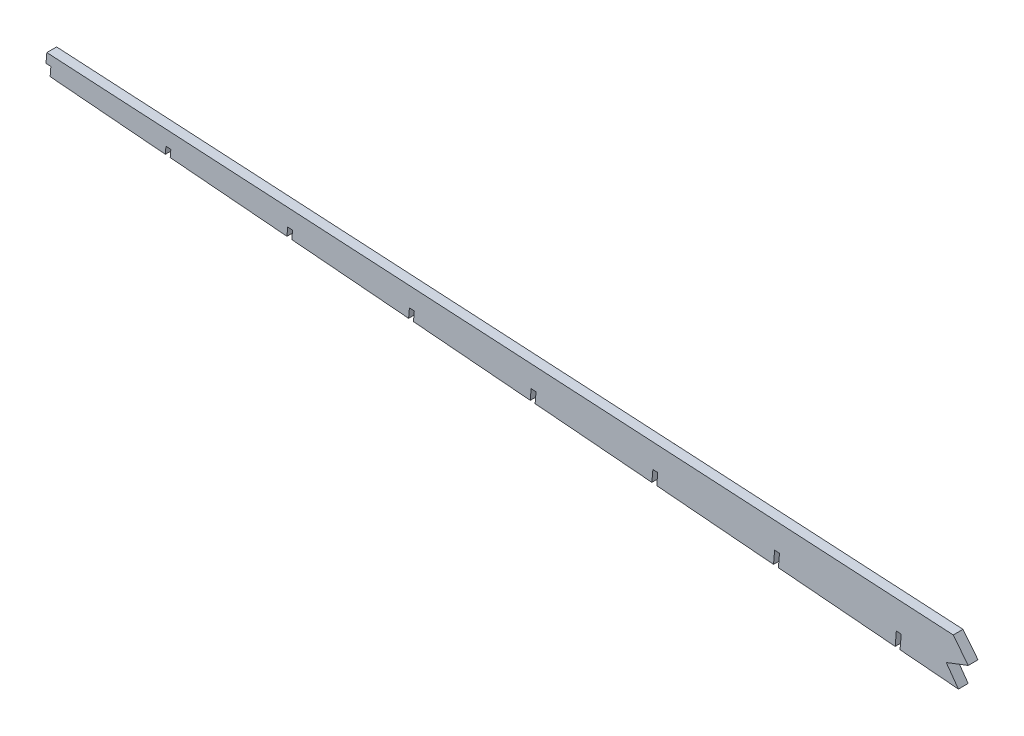
SolidWorks part; units mm, degrees
material "Balsa"
ref_plane "Front Plane" through (0, 0, 0) normal (0, 0, 1) x (1, 0, 0)
ref_plane "Top Plane" through (0, 0, 0) normal (0, 1, 0) x (1, 0, 0)
ref_plane "Right Plane" through (0, 0, 0) normal (1, 0, 0) x (0, 0, -1)
sketch "Sketch1" plane through (0, 0, 0) normal (0, 0, 1) x (1, 0, 0)
  line L0 (76.2, 56.7475) -> (76.2, 37.6975)
  line L1 (79.375, 56.7475) -> (79.375, 37.6975)
  line L2 (0, 44.0475) -> (0, 31.3475)
  line L3 (3.175, 44.0475) -> (3.175, 31.3475)
  line L4 (-5.7133, 44.4467) -> (-6.776, 31.7912)
  line L5 (-2.5494, 44.181) -> (-3.6121, 31.5255)
  line L6 (-1.4923, 31.3475) -> (25.4, 31.3475)
  line L7 (25.4, 31.3475) -> (69.85, 37.6975)
  line L8 (-2.5494, 44.181) -> (-0.424, 69.4919) construction
  line L9 (-0.424, 69.4919) -> (-3.5879, 69.7576)
  line L10 (-3.5879, 69.7576) -> (-5.7133, 44.4467) construction
  line L11 (-5.7133, 44.4467) -> (-2.5494, 44.181)
  line L12 (3.175, 44.0475) -> (3.175, 69.4475) construction
  line L13 (3.175, 69.4475) -> (0, 69.4475)
  line L14 (0, 69.4475) -> (0, 44.0475) construction
  line L15 (0, 44.0475) -> (3.175, 44.0475)
  line L16 (92.075, 37.6975) -> (92.075, 46.5875)
  line L17 (-942.8808, 122.7744) -> (-947.5199, 67.5279)
  line L18 (0, 69.4475) -> (-0.424, 69.4919)
  line L19 (3.175, 69.4475) -> (152.4, 69.4475)
  line L20 (152.4, 69.4475) -> (152.4, 37.6975)
  line L21 (152.4, 37.6975) -> (69.85, 37.6975)
  line L22 (92.075, 46.5875) -> (95.25, 46.5875)
  line L23 (95.25, 46.5875) -> (95.25, 37.6975)
  line L24 (-1.4923, 31.3475) -> (-943.9128, 110.4848)
  line L25 (79.375, 69.4475) -> (79.375, 56.7475)
  line L26 (-942.8808, 122.7744) -> (-3.5879, 69.7576)
  line L27 (136.525, 37.6975) -> (136.525, 46.5875)
  line L28 (76.2, 69.4475) -> (76.2, 56.7475)
  line L29 (79.375, 56.7475) -> (76.2, 56.7475)
  line L30 (-943.5688, 114.5813) -> (-5.7133, 44.4467)
  line L31 (136.525, 46.5875) -> (139.7, 46.5875)
  line L32 (139.7, 46.5875) -> (139.7, 37.6975)
  line L33 (15.875, 31.3475) -> (15.875, 36.4275)
  line L34 (15.875, 36.4275) -> (19.05, 36.4275)
  line L35 (19.05, 36.4275) -> (19.05, 31.3475)
  line L36 (-942.8808, 122.7744) -> (-946.0519, 122.9534)
  line L37 (-946.0519, 122.9534) -> (-946.5835, 116.6233)
  line L38 (-946.5835, 116.6233) -> (-943.4123, 116.4443)
  dimension "D3" = 76.2
  dimension "D10" = 12.3329
  dimension "D11" = 8.2219
  dimension "D2" = 25.4
  dimension "D4" = 25.4
  dimension "D5" = 12.7
  dimension "D7" = 3.175
  dimension "D9" = 3.175
  dimension "D12" = 3.175
  dimension "D6" = 19.05
  dimension "D13" = 6.35
  dimension "D14" = 12.7
  dimension "D16" = 3.175
  dimension "D17" = 3.175
  dimension "D18" = 12.7
  dimension "D19" = 12.7
  dimension "D20" = 8.89
  dimension "D21" = 8.89
  dimension "D15" = 76.2
  dimension "D22" = 12.7
  dimension "D23" = 3.175
  dimension "D24" = 5.08
  dimension "D8" = 6.35
  dimension "D25" = 3.175
  dimension "D26" = 6.35
extrude "Boss-Extrude1" add sketch "Sketch1" along normal mid plane 6.35 contours L17 L30 L11 L5 L24 L6 L2 L15 L3 L7 L21 L0 L28 L19 L13 L18 L9 L26 | L30 L17 L24 L4 | L29 L25 L19 L28 | L19 L25 L1 L21 L20 | L37 L38 L17 L36 region at (-328.9931, 77.9728, 0) region at (77.7875, 63.0975, 0) region at (115.8875, 53.8578, 0) region at (-944.7321, 119.6988, 0) region at (-395.1618, 68.9894, 0)
sketch "Sketch2" plane through (0, 0, 3.175) normal (0, 0, 1) x (1, 0, 0)
  line L2 (-73.2652, 73.2231) -> (-80.3969, -11.7061)
  line L3 (-943.5688, 114.5813) -> (-5.7133, 44.4467)
  line L6 (-76.4291, 73.4888) -> (-83.5608, -11.4404)
  line L7 (-6.776, 31.7912) -> (-943.9128, 110.4848)
  line L10 (-152.4177, 77.6821) -> (-159.3225, -4.5442)
  line L14 (-155.5816, 77.9478) -> (-162.4863, -4.2785)
  line L18 (-231.5658, 82.1932) -> (-238.251, 2.5812)
  line L22 (-234.7297, 82.4589) -> (-241.4149, 2.8469)
  line L26 (-310.7178, 86.6582) -> (-317.1769, 9.7387)
  line L30 (-313.8817, 86.9239) -> (-320.3408, 10.0043)
  line L34 (-389.8657, 91.1713) -> (-396.1056, 16.8623)
  line L38 (-393.0296, 91.437) -> (-399.2695, 17.128)
  line L42 (-469.0186, 95.6263) -> (-475.031, 24.0265)
  line L46 (-472.1824, 95.892) -> (-478.1948, 24.2921)
  line L50 (-548.1666, 100.1381) -> (-553.9596, 31.1506)
  line L54 (-551.3305, 100.4038) -> (-557.1235, 31.4163)
  line L58 (-627.3195, 104.5918) -> (-632.8849, 38.3152)
  line L62 (-630.4834, 104.8575) -> (-636.0488, 38.5809)
  line L66 (-706.4673, 109.1069) -> (-711.8138, 45.4365)
  line L70 (-709.6312, 109.3725) -> (-714.9777, 45.7022)
  line L74 (-785.6206, 113.5558) -> (-790.7389, 52.6041)
  line L78 (-788.7845, 113.8214) -> (-793.9027, 52.8697)
  line L82 (-864.7684, 118.071) -> (-869.6679, 59.7246)
  line L86 (-867.9323, 118.3366) -> (-872.8317, 59.9902)
  line L89 (-942.9091, 122.4365) -> (-947.5795, 66.8182)
  line M2 (-943.9128, 110.4848) -> (-6.776, 31.7912)
extrude "Cut-Extrude1" cut sketch "Sketch2" against normal through all contours L3 L6 L2 M2 | L3 L14 L7 L10 | L3 L22 L7 L18 | L3 L30 L7 L26 | L3 L38 L7 L34 | L3 L46 L7 L42 | L3 L54 L7 L50 | L3 L62 L7 L58 | L3 L70 L7 L66 | L3 L78 L7 L74 | L3 L86 L7 L82 region at (-77.3317, 43.7615, 3.175) region at (-156.332, 50.0322, 3.175) region at (-235.3323, 56.3029, 3.175) region at (-314.3326, 62.5736, 3.175) region at (-393.3328, 68.8442, 3.175) region at (-472.3331, 75.1149, 3.175) region at (-551.3334, 81.3856, 3.175) region at (-630.3336, 87.6563, 3.175) region at (-709.3339, 93.9269, 3.175) region at (-788.334, 100.1976, 3.175) region at (-867.3342, 106.4683, 3.175)
sketch "Sketch3" plane through (0, 0, 3.175) normal (0, 0, 1) x (1, 0, 0)
  line L0 (-354.2316, 60.9679) -> (-362.1267, 71.9794)
  line L1 (-316.3285, 57.7851) -> (-392.1347, 64.1507) construction
  line L2 (-362.1267, 71.9794) -> (-347.8724, 77.4491)
  line L3 (-347.8724, 77.4491) -> (-357.599, 89.7392)
  line L4 (-946.0519, 122.9534) -> (-3.5879, 69.7576) construction
  line L5 (-357.599, 89.7392) -> (194.2184, 89.7392)
  line L6 (194.2184, 89.7392) -> (127.8118, -85.756)
  line L7 (127.8118, -85.756) -> (-354.2316, 60.9679)
extrude "Cut-Extrude2" cut sketch "Sketch3" against normal blind 7.62 contours L7 L0 L2 L3 L5 L6
equation "\"D11@Sketch1\"=\"D10@Sketch1\"*(2/3)"
